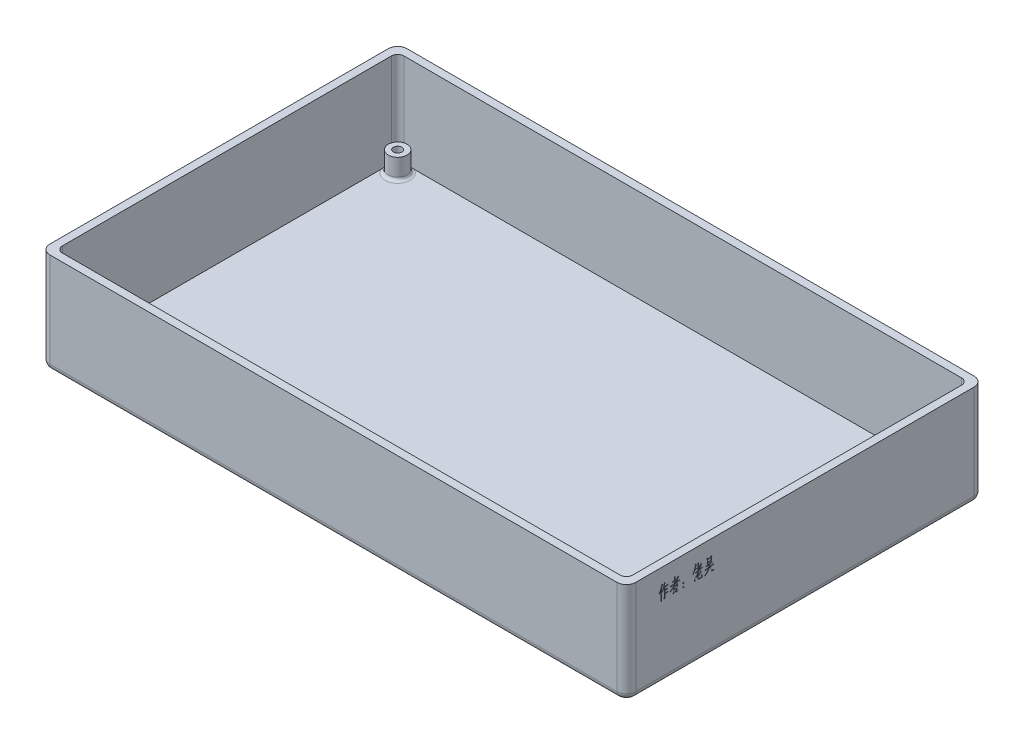
SolidWorks part; units mm, degrees
other "标注2"
sketch "草图4" plane through (0, 70, 0) normal (-0.4367, 0.7015, 0.5633) x (0.8757, 0.4749, 0.0875)
ref_plane "前视基准面" through (0, 0, 0) normal (0, 0, 1) x (1, 0, 0)
ref_plane "上视基准面" through (0, 0, 0) normal (0, 1, 0) x (1, 0, 0)
ref_plane "右视基准面" through (0, 0, 0) normal (1, 0, 0) x (0, 0, -1)
sketch "草图1" plane through (0, 0, 0) normal (0, 1, 0) x (1, 0, 0)
  line L1 (0, 0) -> (187, 0)
  line L2 (0, 0) -> (0, 114)
  line L3 (0, 114) -> (187, 114)
  line L4 (187, 0) -> (187, 114)
  point P5 (93.5, 114)
  dimension "D1" = 114
  dimension "D2" = 187
extrude "凸台-拉伸1" add sketch "草图1" along normal blind 32.2
shell "抽壳1" thickness 2.5 removed face at (93.5, 32.2, -57)
fillet "圆角1" radius 3 1 edges at (0, 16.1, -114)
fillet "圆角2" radius 2 1 edges at (2.5, 17.35, -111.5)
fillet "圆角3" radius 3 3 edges at (187, 16.1, -114) (187, 16.1, 0) (0, 16.1, 0)
fillet "圆角4" radius 2 3 edges at (2.5, 17.35, -2.5) (184.5, 17.35, -2.5) (184.5, 17.35, -111.5)
fillet "圆角5" radius 2 8 edges at (186.1213, 0, -0.8787) (187, 0, -57) (186.1213, 0, -113.1213) (93.5, 0, -114) (0.8787, 0, -113.1213) (0, 0, -57) (0.8787, 0, -0.8787) (93.5, 0, 0)
sketch "草图2" plane through (0, 2.5, 0) normal (0, 1, 0) x (1, 0, 0)
  line L0 (2.5, 57) -> (184.5, 57) construction
  line L1 (2.5, 109.5) -> (2.5, 4.5) construction
  line L2 (184.5, 4.5) -> (184.5, 109.5) construction
  line L3 (93.5, -11.6108) -> (93.5, 125.6108) construction
  circle A0 centre (6.2, 107.8) radius 1.35
  circle A1 centre (6.2, 107.8) radius 3
  circle A2 centre (180.8, 107.8) radius 3
  circle A3 centre (180.8, 107.8) radius 1.35
  circle A4 centre (180.8, 6.2) radius 1.35
  circle A5 centre (180.8, 6.2) radius 3
  circle A6 centre (6.2, 6.2) radius 3
  circle A7 centre (6.2, 6.2) radius 1.35
  point P9 (93.5, 57)
  dimension "D1" = 2.7
  dimension "D2" = 6
  dimension "D3" = 87.3
  dimension "D4" = 50.8
extrude "凸台-拉伸2" add sketch "草图2" along normal blind 6.5
fillet "圆角6" radius 1 1 edges at (180.8, 2.5, -9.2)
fillet "圆角7" radius 1 3 edges at (6.2, 2.5, -9.2) (6.2, 2.5, -110.8) (180.8, 2.5, -110.8)
sketch "草图5" plane through (187, 0, 0) normal (1, 0, 0) x (0, 0, -1)
  text T0 "作者：佬吴"
extrude "切除-拉伸1" cut sketch "草图5" against normal blind 0.2
